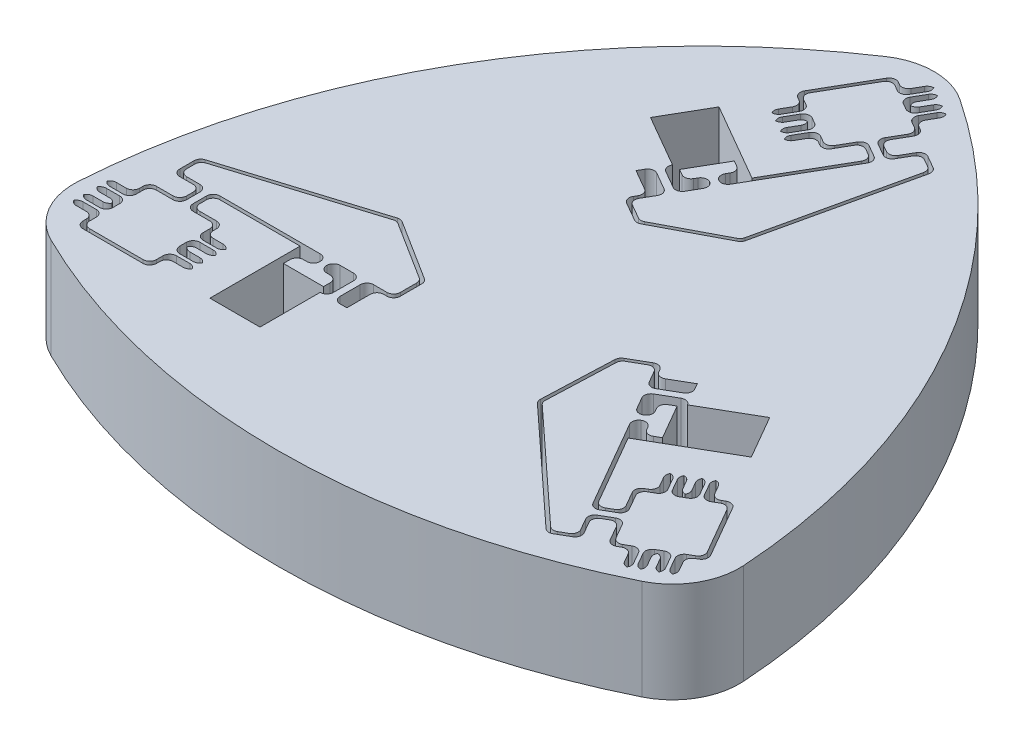
SolidWorks part; units mm, degrees
material "7050-T73510"
ref_plane "Front Plane" through (0, 0, 0) normal (0, 0, 1) x (1, 0, 0)
ref_plane "Top Plane" through (0, 0, 0) normal (0, 1, 0) x (1, 0, 0)
ref_plane "Right Plane" through (0, 0, 0) normal (1, 0, 0) x (0, 0, -1)
sketch "Bass" plane through (0, 0, 0) normal (0, 1, 0) x (1, 0, 0)
  line L1 (0, 57.735) -> (-50, -28.8675) construction
  line L2 (-50, -28.8675) -> (50, -28.8675) construction
  line L3 (50, -28.8675) -> (0, 57.735) construction
  circle A0 centre (0, 0) radius 28.8675 construction
  arc A1 (0, 57.735) -> (50, -28.8675) centre (-50, -28.8675) cw
  arc A2 (-50, -28.8675) -> (0, 57.735) centre (50, -28.8675) cw
  arc A3 (-50, -28.8675) -> (50, -28.8675) centre (0, 57.735) ccw
  dimension "D1" = 100
extrude "Drop the" add sketch "Bass" against normal blind 15
sketch "Flexin" plane through (0, 0, 0) normal (0, -1, 0) x (1, 0, 0)
  line L0 (-8.4558, -22.5533) -> (-7.9558, -23.4193)
  line L1 (-7.9558, -23.4193) -> (-3.6256, -20.9193)
  line L2 (-3.6256, -20.9193) -> (-1.6256, -24.3834)
  line L5 (-1.6256, -24.3834) -> (-3.3577, -25.3834)
  line L6 (-3.3577, -25.3834) -> (-4.6077, -23.2184)
  line L7 (-4.6077, -23.2184) -> (-6.3397, -24.2184)
  line L8 (-6.3397, -24.2184) -> (-3.3397, -29.4145)
  line L9 (-3.3397, -29.4145) -> (-1.6077, -28.4145)
  line L10 (-1.6077, -28.4145) -> (-2.8577, -26.2495)
  line L11 (-2.8577, -26.2495) -> (-1.1256, -25.2495)
  line L14 (-1.1256, -25.2495) -> (7.3744, -39.9719)
  line L15 (7.3744, -39.9719) -> (3.9103, -41.9719)
  line L16 (3.9103, -41.9719) -> (1.6603, -38.0748)
  line L17 (1.6603, -38.0748) -> (-0.9378, -39.5748)
  line L18 (-0.9378, -39.5748) -> (-2.9378, -36.1107)
  line L19 (-2.9378, -36.1107) -> (-3.3708, -36.3607)
  line L20 (-3.3708, -36.3607) -> (-1.3708, -39.8248)
  line L21 (-1.3708, -39.8248) -> (-3.9689, -41.3248)
  line L22 (-3.9689, -41.3248) -> (-5.9689, -37.8607)
  line L23 (-5.9689, -37.8607) -> (-6.4019, -38.1107)
  line L24 (-6.4019, -38.1107) -> (-4.4019, -41.5748)
  line L25 (-4.4019, -41.5748) -> (-7, -43.0748)
  line L26 (-7, -43.0748) -> (-2, -51.735)
  line L27 (-2, -51.735) -> (0.5981, -50.235)
  line L28 (0.5981, -50.235) -> (2.5981, -53.6991)
  line L29 (2.5981, -53.6991) -> (3.0311, -53.4491)
  line L30 (3.0311, -53.4491) -> (1.0311, -49.985)
  line L31 (1.0311, -49.985) -> (3.6292, -48.485)
  line L32 (3.6292, -48.485) -> (5.6292, -51.9491)
  line L33 (5.6292, -51.9491) -> (6.0622, -51.6991)
  line L34 (6.0622, -51.6991) -> (4.0622, -48.235)
  line L35 (4.0622, -48.235) -> (6.6603, -46.735)
  line L36 (6.6603, -46.735) -> (4.4103, -42.8379)
  line L37 (4.4103, -42.8379) -> (7.8744, -40.8379)
  line L38 (7.8744, -40.8379) -> (9.8744, -44.302)
  line L39 (9.8744, -44.302) -> (12.4724, -42.802)
  line L40 (12.4724, -42.802) -> (7.2846, -19.8164)
  line L41 (7.2846, -19.8164) -> (-2.6615, -14.5892)
  line L42 (-2.6615, -14.5892) -> (-6.1256, -16.5892)
  line L43 (-6.1256, -16.5892) -> (-4.1256, -20.0533)
  line L44 (-4.1256, -20.0533) -> (-8.4558, -22.5533)
  line L45 (-8.2058, -22.9863) -> (-3.8756, -20.4863) construction
  line L46 (-4.8397, -26.8164) -> (-1.3756, -24.8164) construction
  line L47 (-4.5, -47.4049) -> (7.6244, -40.4049) construction
  line L48 (-15.25, -28.7854) -> (-7.4558, -24.2854)
  line L49 (-7.4558, -24.2854) -> (-7.9558, -23.4193)
  line L50 (6.9282, -51.1991) -> (6.0622, -51.6991)
  line L51 (4.7631, -52.4491) -> (5.6292, -51.9491)
  line L52 (3.8971, -52.9491) -> (3.0311, -53.4491)
  line L53 (-15.25, -28.7854) -> (-11.5, -35.2805)
  line L54 (-11.5, -35.2805) -> (0.1913, -28.5305)
  line L55 (2.5981, -53.6991) -> (1.7321, -54.1991)
  line L56 (-5.1029, -37.3607) -> (-5.9689, -37.8607)
  line L57 (0.1913, -28.5305) -> (6.6913, -39.7889)
  line L58 (6.6913, -39.7889) -> (4.0933, -41.2889)
  line L59 (4.0933, -41.2889) -> (1.8433, -37.3918)
  line L60 (1.8433, -37.3918) -> (-0.3218, -38.6418)
  line L61 (-0.3218, -38.6418) -> (-2.0718, -35.6107)
  line L62 (-4.2369, -36.8607) -> (-2.4869, -39.8918)
  line L63 (-2.4869, -39.8918) -> (-3.3529, -40.3918)
  line L64 (-3.3529, -40.3918) -> (-5.1029, -37.3607)
  line L65 (-7.2679, -38.6107) -> (-5.5179, -41.6418)
  line L66 (-5.5179, -41.6418) -> (-7.683, -42.8918)
  line L67 (-7.683, -42.8918) -> (-2.183, -52.418)
  line L68 (-2.183, -52.418) -> (-0.0179, -51.168)
  line L69 (-0.0179, -51.168) -> (1.7321, -54.1991)
  line L70 (-6.4019, -38.1107) -> (-7.2679, -38.6107)
  line L71 (3.8971, -52.9491) -> (2.1471, -49.918)
  line L72 (2.1471, -49.918) -> (3.0131, -49.418)
  line L73 (3.0131, -49.418) -> (4.7631, -52.4491)
  line L74 (-2.0718, -35.6107) -> (-2.9378, -36.1107)
  line L75 (6.9282, -51.1991) -> (5.1782, -48.168)
  line L76 (5.1782, -48.168) -> (7.3433, -46.918)
  line L77 (7.3433, -46.918) -> (5.0933, -43.0209)
  line L78 (5.0933, -43.0209) -> (7.6913, -41.5209)
  line L79 (7.6913, -41.5209) -> (9.6913, -44.985)
  line L80 (9.6913, -44.985) -> (13.0412, -43.051)
  line L81 (13.0412, -43.051) -> (7.7215, -19.4812)
  line L82 (7.7215, -19.4812) -> (-2.6729, -14.0184)
  line L83 (-2.6729, -14.0184) -> (-6.8087, -16.4062)
  line L84 (-6.8087, -16.4062) -> (-5.5587, -18.5713)
  line L85 (-5.5587, -18.5713) -> (-9.4558, -20.8213)
  line L88 (-8.4558, -22.5533) -> (-9.4558, -20.8213)
  line L89 (-3.3708, -36.3607) -> (-4.2369, -36.8607)
  point P4 (0, 0)
  point P87 (-1.9917, -25.7495)
  dimension "D1" = 4
  dimension "D2" = 1
  dimension "D3" = 4
  dimension "D4" = 1
  dimension "D5" = 5
  dimension "D6" = 1
  dimension "D7" = 10
  dimension "D8" = 10
  dimension "D9" = 17
  dimension "D10" = 18
  dimension "D11" = 0.5
  dimension "D12" = 3
  dimension "D13" = 3
  dimension "D14" = 4
  dimension "D15" = 2
  dimension "D16" = 6
  dimension "D17" = 4
  dimension "D18" = 4
  dimension "D19" = 4
  dimension "D20" = 10
  dimension "D21" = 32
  dimension "D22" = 4
  dimension "D23" = 3
  dimension "D24" = 5
  dimension "D25" = 0.5
  dimension "D26" = 0.5
  dimension "D27" = 0.5
  dimension "D28" = 0.5
  dimension "D29" = 0.5
  dimension "D30" = 0.5
  dimension "D31" = 0.5
  dimension "D32" = 0.5
  dimension "D33" = 1
  dimension "D34" = 1
  dimension "D35" = 1
  dimension "D36" = 2
  dimension "D37" = 0.5
  dimension "D38" = 10
  dimension "D39" = 1
  dimension "D40" = 1
  dimension "D41" = 1
  dimension "D42" = 1
  dimension "D43" = 1
  dimension "D44" = 1
  dimension "D45" = 1
  dimension "D46" = 6
  dimension "D47" = 2
extrude "Now we" cut sketch "Flexin" along normal through all contours L70 L24 L25 L26 L27 L28 L55 L69 L68 L67 L66 L65 | L73 L72 L71 L52 L30 L31 L32 L51 | L44 L88 L85 L84 L83 L82 L81 L80 L79 L78 L77 L76 L75 L50 L34 L35 L36 L37 L38 L39 L40 L41 L42 L43 | L74 L61 L60 L59 L58 L57 L54 L53 L48 L49 L1 L2 L5 L6 L7 L8 L9 L10 L11 L14 L15 L16 L17 L18 | L89 L20 L21 L22 L56 L64 L63 L62 region at (-8.5757, 0, -21.4678) region at (-6.3332, 0, -29.7343) region at (-2.4294, 0, -38.1266) region at (5.1623, 0, -52.1405) region at (-5.5673, 0, -39.9382)
fillet "Flexy Fish" radius 1 69 edges at (5.0933, -7.5, -43.0209) (4.4103, -7.5, -42.8379) (7.8744, -7.5, -40.8379) (7.6913, -7.5, -41.5209) (7.3744, -7.5, -39.9719) (6.6913, -7.5, -39.7889) (4.0933, -7.5, -41.2889) (3.9103, -7.5, -41.9719) (-2.6729, -7.5, -14.0184) (-2.6615, -7.5, -14.5892) (7.2846, -7.5, -19.8164) (7.7215, -7.5, -19.4812) (12.4724, -7.5, -42.802) (13.0412, -7.5, -43.051) (9.6913, -7.5, -44.985) (9.8744, -7.5, -44.302) (-7.9558, -7.5, -23.4193) (-8.4558, -7.5, -22.5533) (-4.1256, -7.5, -20.0533) (-5.5587, -7.5, -18.5713) (-6.1256, -7.5, -16.5892) (-6.8087, -7.5, -16.4062) (-2.8577, -7.5, -26.2495) (-1.1256, -7.5, -25.2495) (-1.6256, -7.5, -24.3834) (-3.3577, -7.5, -25.3834) (-3.6256, -7.5, -20.9193) (5.6292, -7.5, -51.9491) (6.0622, -7.5, -51.6991) (3.0131, -7.5, -49.418) (3.6292, -7.5, -48.485) (5.1782, -7.5, -48.168) (4.0622, -7.5, -48.235) (7.3433, -7.5, -46.918) (6.6603, -7.5, -46.735) (-2.183, -7.5, -52.418) (-2, -7.5, -51.735) (1.7321, -7.5, -54.1991) (-0.0179, -7.5, -51.168) (1.0311, -7.5, -49.985) (3.0311, -7.5, -53.4491) (4.7631, -7.5, -52.4491) (2.1471, -7.5, -49.918) (3.8971, -7.5, -52.9491) (2.5981, -7.5, -53.6991) (-2.0718, -7.5, -35.6107) (-2.9378, -7.5, -36.1107) (6.9282, -7.5, -51.1991) (-7.2679, -7.5, -38.6107) (-6.4019, -7.5, -38.1107) (-5.9689, -7.5, -37.8607) (-5.1029, -7.5, -37.3607) (-3.3708, -7.5, -36.3607) (-4.2369, -7.5, -36.8607) (1.8433, -7.5, -37.3918) (1.6603, -7.5, -38.0748) (-0.3218, -7.5, -38.6418) (-0.9378, -7.5, -39.5748) (-1.3708, -7.5, -39.8248) (-2.4869, -7.5, -39.8918) (-3.3529, -7.5, -40.3918) (-3.9689, -7.5, -41.3248) (-4.4019, -7.5, -41.5748) (-5.5179, -7.5, -41.6418) (-7.683, -7.5, -42.8918) (-7, -7.5, -43.0748) (0.5981, -7.5, -50.235) (-4.6077, -7.5, -23.2184) (-1.6077, -7.5, -28.4145)
fillet "Fillet o' Bass" radius 10 3 edges at (50, -7.5, 28.8675) (-50, -7.5, 28.8675) (0, -7.5, -57.735)
sketch "Reference Top Plane" plane through (0, 0, 0) normal (0, 1, 0) x (1, 0, 0)
  line L0 (-1000, 0) -> (49000, 0) construction
  line L1 (0, -1000) -> (0, 49000) construction
sketch "Reference Y-Axis" plane through (0, 0, 0) normal (1, 0, 0) x (0, 0, -1)
  line L0 (0, -1000) -> (0, 49000) construction
pattern_circular "Reflexurn" count 3 over 360 about axis through (0, -1000, 0) along (0, 1, 0) of "Now we", "Flexy Fish"
equation "\"offsetDistance\"=0.5"
